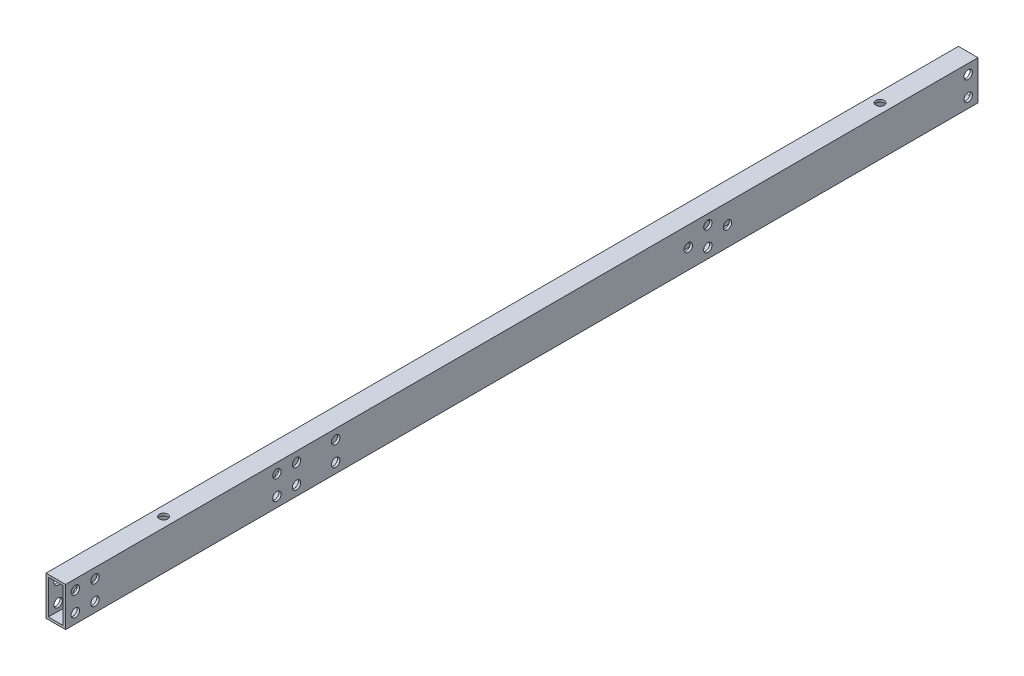
SolidWorks part; units mm, degrees
material "5052-H34"
ref_plane "正面" through (0, 0, 0) normal (0, 0, 1) x (1, 0, 0)
ref_plane "平面" through (0, 0, 0) normal (0, 1, 0) x (1, 0, 0)
ref_plane "右側面" through (0, 0, 0) normal (1, 0, 0) x (0, 0, -1)
sketch "ｽｹｯﾁ1" plane through (0, 0, 0) normal (0, 0, 1) x (1, 0, 0)
  line L1 (-5, 10) -> (5, 10)
  line L2 (-5, 10) -> (-5, -10)
  line L3 (-5, -10) -> (5, -10)
  line L4 (5, 10) -> (5, -10)
  line L5 (-5, 10) -> (5, -10) construction
  line L6 (-5, -10) -> (5, 10) construction
  point P0 (0, 0)
  dimension "D1" = 10
  dimension "D2" = 20
extrude "押し出し-薄板1" add sketch "ｽｹｯﾁ1" along normal blind 465.8 thin thin type one direction reverse wall 1.2
sketch "ｽｹｯﾁ2" plane through (5, 0, 0) normal (1, 0, 0) x (0, 0, -1)
  line L0 (-232.9, 10) -> (-232.9, -10) construction
  line L1 (-465.8, 10) -> (0, 10) construction
  line L2 (-465.8, -10) -> (0, -10) construction
  line L3 (-465.8, 0) -> (-450.8, 0) construction
  line L4 (-465.8, -10) -> (-465.8, 10) construction
  line L5 (-450.8, 0) -> (-450.8, 5) construction
  line L6 (-232.9, 0) -> (-137.9, 0) construction
  line L7 (-137.9, 0) -> (-137.9, 10) construction
  line L8 (-232.9, 0) -> (-327.9, 0) construction
  line L9 (-327.9, 0) -> (-327.9, 5) construction
  line L10 (0, -10) -> (0, 10) construction
  line L11 (-357.9, 0) -> (-357.9, 5) construction
  circle A0 centre (-450.8, 5) radius 2.15
  circle A1 centre (-450.8, -5) radius 2.15
  circle A2 centre (-5, 5) radius 2.15
  circle A3 centre (-5, -5) radius 2.15
  circle A4 centre (-147.9, 0) radius 2.15
  circle A5 centre (-127.9, 0) radius 2.15
  circle A6 centre (-327.9, 5) radius 2.15
  circle A7 centre (-327.9, -5) radius 2.15
  circle A8 centre (-137.9, -5) radius 2.15
  circle A9 centre (-137.9, 5) radius 2.15
  circle A10 centre (-357.9, 5) radius 2.15
  circle A11 centre (-357.9, -5) radius 2.15
  circle A12 centre (-347.9, -5) radius 2.15
  circle A13 centre (-347.9, 5) radius 2.15
  circle A14 centre (-460.8, 5) radius 2.15
  circle A15 centre (-460.8, -5) radius 2.15
  point P40 (0, 0)
  dimension "D2" = 4.3
  dimension "D5" = 4.3
  dimension "D7" = 4.3
  dimension "D10" = 4.3
  dimension "D15" = 4.3
  dimension "D16" = 5
  dimension "D17" = 5
  dimension "D19" = 445.8
  dimension "D3" = 10
  dimension "D4" = 95
  dimension "D6" = 20
  dimension "D8" = 10
  dimension "D9" = 190
  dimension "D11" = 10
  dimension "D12" = 220
  dimension "D14" = 10
  dimension "D18" = 5
  dimension "D20" = 5
  dimension "D13" = 2
extrude "ｶｯﾄ - 押し出し1" cut sketch "ｽｹｯﾁ2" against normal through all contours A6 | A7 | A12 | A13 | A0 | A1 | A9 | A8 | A4 | A5 | A2 | A3 | A10 | A11 | A14 | A15 region at (5, 5, 450.8) region at (5, -5, 450.8) region at (5, 5, 5) region at (5, -5, 5) region at (5, 0, 147.9) region at (5, 0, 127.9) region at (5, 5, 327.9) region at (5, -5, 327.9) region at (5, -5, 137.9) region at (5, 5, 137.9) region at (5, 5, 357.9) region at (5, -5, 357.9) region at (5, -5, 347.9) region at (5, 5, 347.9)
sketch "ｽｹｯﾁ3" plane through (0, 10, 0) normal (0, 1, 0) x (1, 0, 0)
  line L0 (0, -465.8) -> (0, -410.8) construction
  line L1 (5, -465.8) -> (-5, -465.8) construction
  line L2 (-5, -232.9) -> (5, -232.9) construction
  line L3 (-5, -465.8) -> (-5, 0) construction
  line L4 (5, -465.8) -> (5, 0) construction
  line L5 (5, 0) -> (-5, 0) construction
  circle A0 centre (0, -410.8) radius 2.15
  circle A1 centre (0, -45) radius 2.15
  point P14 (0, 0)
  point P17 (0, 0)
  dimension "D2" = 4.3
  dimension "D3" = 45
  dimension "D1" = 55
extrude "ｶｯﾄ - 押し出し2" cut sketch "ｽｹｯﾁ3" against normal through all
